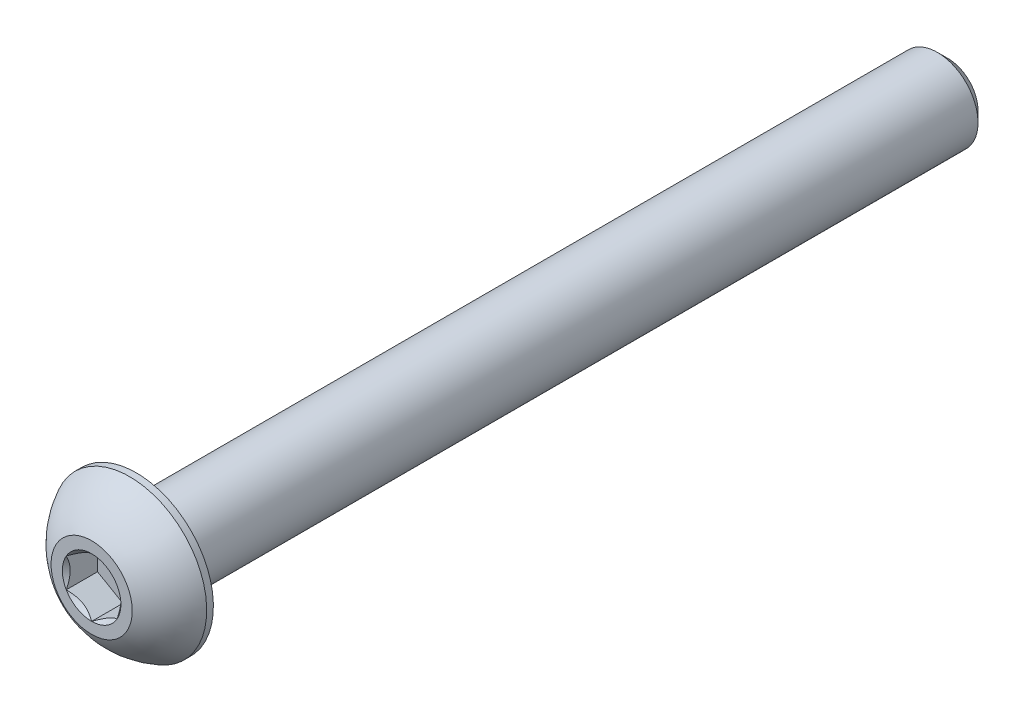
SolidWorks part; units mm, degrees
ref_plane "Front" through (0, 0, 0) normal (0, 0, 1) x (1, 0, 0)
ref_plane "Top" through (0, 0, 0) normal (0, 1, 0) x (1, 0, 0)
ref_plane "Right" through (0, 0, 0) normal (1, 0, 0) x (0, 0, -1)
sketch "Sketch1" plane through (0, 0, 0) normal (1, 0, 0) x (0, 0, -1)
  line L2 (-20, 2) -> (20, 2)
  line L3 (20, 2) -> (20, 0)
  line L4 (20, 0) -> (-20, 0)
  line L6 (-20.33, 3.8) -> (-20, 3.8) construction
  line L7 (20, 2) -> (20, -2) construction
  line L8 (-22.2, 0) -> (-20, 0) construction
  line L9 (-20, 3.8) -> (-20, -3.8) construction
  line L11 (-20, 2) -> (-20, 0)
  line L13 (-22.2, 1.25) -> (-22.2, -1.25) construction
  line L14 (-22.2, 1.25) -> (-22.2, 2) construction
  line L15 (19.9563, 2.0758) -> (20.3063, 1.4696) construction
  line L16 (20.3063, 1.4696) -> (20.6563, 2.0758) construction
  line L17 (20.6563, 2.0758) -> (19.9563, 2.0758) construction
  line L18 (20, 2) -> (20.6125, 2) construction
  line L19 (20.3063, 2.0758) -> (20.3063, 2) construction
  line L20 (20.3063, 2) -> (20.3063, 1.5453) construction
  line L21 (20.3063, 1.5453) -> (20.3063, 1.4696) construction
  line L22 (20.2625, 1.5453) -> (20.35, 1.5453)
  line L23 (19.9781, 2.0379) -> (20.6344, 2.0379)
  line L24 (20.35, 1.5453) -> (20.6344, 2.0379)
  line L25 (20.2625, 1.5453) -> (19.9781, 2.0379)
  line L26 (19.475, 2) -> (20, 1.475)
  arc A3 (-22.2, 2) -> (-20.33, 3.8) centre (-18.4736, 0) cw construction
  point P29 (20.3063, 2.0379)
  point P30 (18.25, -2)
  point P32 (0, 2)
  point P33 (-5, 0)
  point P34 (0, 0)
  point P35 (-15, 0)
  dimension "Thread Size" = 4
  dimension "D1" = 0.33
  dimension "Head Height" = 2.2
  dimension "Head Diameter" = 7.6
  dimension "Length" = 40
  dimension "Drive Size" = 2.5
  dimension "Thread Pitch" = 0.7
  dimension "D3" = 0.0875
  dimension "D2" = 0.525
  dimension "D4" = 45
  dimension "D5" = 1.75
  dimension "Minimum Thread Length" = 20
  dimension "D6" = 5
  dimension "D7" = 5
sketch "Sketch10" plane through (0, 0, 0) normal (1, 0, 0) x (0, 0, -1)
  line L0 (19.475, 2) -> (20, 1.475) construction
  line L1 (19.475, 2) -> (20, 1.475)
  line L4 (20, 2) -> (-20, 2)
  line L5 (20, 0) -> (20, 2)
  line L6 (-20, 0) -> (20, 0)
  line L7 (-20, 2) -> (-20, 0)
  line L8 (19.475, 2) -> (-20, 2)
  line L9 (20, 0) -> (20, 1.475)
  line L10 (-20, 0) -> (20, 0)
  line L11 (-20, 2) -> (-20, 0)
  dimension "D1" = 0
revolve "Revolve3" add sketch "Sketch10" angle 360 about L8
sketch "Sketch7" plane through (0, 0, 0) normal (1, 0, 0) x (0, 0, -1)
  line L6 (-20.33, 3.8) -> (-20, 3.8) construction
  line L8 (-22.2, 0) -> (-20, 0) construction
  line L11 (-20, 3.8) -> (-20, -3.8) construction
  line L12 (-20.33, 3.8) -> (-20, 3.8)
  line L13 (-22.2, 0) -> (-20, 0)
  line L14 (-22.2, 1.25) -> (-22.2, -1.25) construction
  line L15 (-20, 3.8) -> (-20, 0)
  line L16 (-22.2, 2) -> (-22.2, 0)
  arc A2 (-20.33, 3.8) -> (-22.2, 2) centre (-18.4736, 0) ccw construction
  arc A3 (-20.33, 3.8) -> (-22.2, 2) centre (-18.4736, 0) ccw
revolve "Revolve2" add sketch "Sketch7" angle 360 mid plane about L13
sketch "Sketch5" plane through (0, 0, 22.2) normal (0, 0, 1) x (1, 0, 0)
  line L1 (1.25, -0.7217) -> (1.25, 0.7217)
  line L2 (1.25, 0.7217) -> (0, 1.4434)
  line L3 (0, 1.4434) -> (-1.25, 0.7217)
  line L4 (-1.25, 0.7217) -> (-1.25, -0.7217)
  line L5 (-1.25, -0.7217) -> (0, -1.4434)
  line L6 (0, -1.4434) -> (1.25, -0.7217)
  circle A0 centre (0, 0) radius 1.25 construction
extrude "Cut-Extrude2" cut sketch "Sketch5" against normal blind 1.54
sketch "Sketch6" plane through (0, 0, 22.2) normal (0, 0, 1) x (1, 0, 0)
  circle A0 centre (0, 0) radius 1.4434
extrude "Cut-Extrude3" cut sketch "Sketch6" against normal blind 1.54 draft 45
ref_plane "Plane1" through (0, 0, 0) normal (0, 0, 1) x (1, 0, 0)
sketch "Sketch9" [suppressed] plane through (0, 0, 0) normal (0, 0, -1) x (-1, 0, 0)
  circle A0 centre (0, 0) radius 2 construction
  circle A4 centre (0, 0) radius 2
split "Split1" [suppressed] bodies to split 113
sketch "Sketch11" [suppressed] plane through (0, 0, -20) normal (0, 0, -1) x (-1, 0, 0)
  circle A0 centre (0, 0) radius 2 construction
  circle A1 centre (0, 0) radius 2
curve "Helix/Spiral1" [suppressed] pitch 0.7 height 22.2 turns 31.7143
sketch "Sketch12" [suppressed] plane through (0, 0, 0) normal (1, 0, 0) x (0, 0, -1)
  line L0 (20.2625, 1.5453) -> (20.35, 1.5453) construction
  line L1 (20.35, 1.5453) -> (20.6344, 2.0379) construction
  line L2 (19.9781, 2.0379) -> (20.6344, 2.0379) construction
  line L3 (20.2625, 1.5453) -> (19.9781, 2.0379) construction
  line L4 (20.2625, 1.5453) -> (20.35, 1.5453)
  line L5 (20.35, 1.5453) -> (20.6344, 2.0379)
  line L6 (19.9781, 2.0379) -> (20.6344, 2.0379)
  line L7 (20.2625, 1.5453) -> (19.9781, 2.0379)
sweep "Cut-Sweep2" [suppressed] cut profiles "Sketch12" path "Helix/Spiral1"
extrude "Boss-Extrude1" [suppressed] add sketch "Sketch9" along normal blind 10 draft 45
equation "\"D1@Cut-Extrude2\" = \"Head Height@Sketch1\" * .7"
equation "\"D1@Sketch1\" = \"Head Height@Sketch1\" * .15"
equation "\"D1@Cut-Extrude3\" = \"D1@Cut-Extrude2\""
equation "\"D3@Sketch1\" = \"Thread Pitch@Sketch1\" / 8"
equation "\"D2@Sketch1\" = \"Thread Pitch@Sketch1\" * 0.75"
equation "\"D3@Helix/Spiral1\"=\"Minimum Thread Length@Sketch1\" + \"Head Height@Sketch1\""
equation "\"D4@Helix/Spiral1\" = \"Thread Pitch@Sketch1\""
equation "\"D5@Sketch1\" = \"Thread Pitch@Sketch1\" * 2.5"
